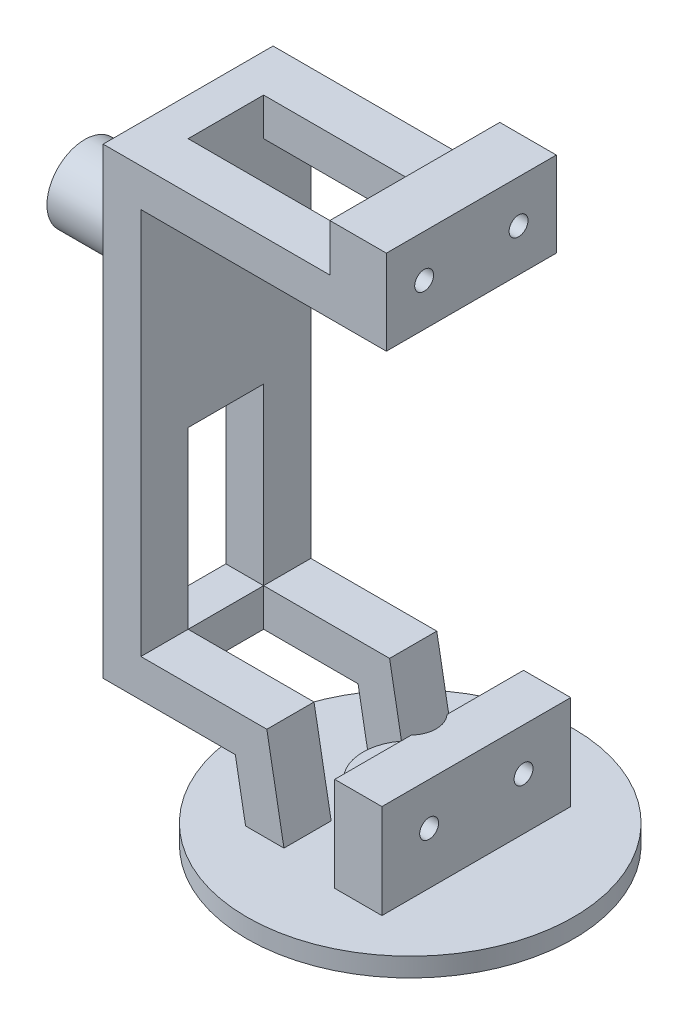
SolidWorks part; units mm, degrees
ref_plane "Front Plane" through (0, 0, 0) normal (0, 0, 1) x (1, 0, 0)
ref_plane "Top Plane" through (0, 0, 0) normal (0, 1, 0) x (1, 0, 0)
ref_plane "Right Plane" through (0, 0, 0) normal (1, 0, 0) x (0, 0, -1)
sketch "Sketch1" plane through (0, 0, 0) normal (0, 1, 0) x (1, 0, 0)
  line L0 (-20, 0) -> (20, 0) construction
  line L1 (-20, -12.5) -> (20, -12.5)
  line L2 (-20, -12.5) -> (-20, 12.5)
  line L3 (-20, 12.5) -> (20, 12.5)
  line L4 (20, -12.5) -> (20, 12.5)
  line L5 (-20, -12.5) -> (20, 12.5) construction
  line L6 (-20, 12.5) -> (20, -12.5) construction
  line L7 (0, 12.5) -> (0, -12.5) construction
  line L8 (-7.9106, 3.9553) -> (7.0894, 3.9553)
  line L9 (-7.9106, 3.9553) -> (-7.9106, -3.5447)
  line L10 (-7.9106, -3.5447) -> (7.0894, -3.5447)
  line L11 (7.0894, 3.9553) -> (7.0894, -3.5447)
  line L12 (-7.9106, 3.9553) -> (7.0894, -3.5447) construction
  line L13 (-7.9106, -3.5447) -> (7.0894, 3.9553) construction
  circle A0 centre (0, 7.9553) radius 1
  circle A1 centre (0, -7.5447) radius 1
  circle A2 centre (16, 0) radius 1
  circle A3 centre (-16, 0) radius 1
  point P0 (0, 0)
  point P8 (0, 0)
  dimension "D5" = 2
  dimension "D7" = 2
  dimension "D9" = 2
  dimension "D1" = 40
  dimension "D2" = 25
  dimension "D3" = 15
  dimension "D4" = 7.5
  dimension "D6" = 4
  dimension "D8" = 4
  dimension "D10" = 16
extrude "Boss-Extrude1" add sketch "Sketch1" along normal blind 2 contours L2 L1 L4 L3
sketch "Sketch2" plane through (0, 2, 0) normal (0, 1, 0) x (1, 0, 0)
  line L1 (2, 10) -> (7, 10)
  line L2 (2, 10) -> (2, -10)
  line L3 (2, -10) -> (7, -10)
  line L4 (7, 10) -> (7, -10)
  line L5 (20, -12.5) -> (20, 12.5) construction
  point P6 (20, 0)
  point P7 (7, 0)
  dimension "D1" = 20
  dimension "D2" = 13
  dimension "D3" = 5
extrude "Boss-Extrude2" add sketch "Sketch2" along normal blind 10
sketch "Sketch4" plane through (7, 0, 0) normal (1, 0, 0) x (0, 0, -1)
  line L0 (-7.046, 10.16) -> (2.954, 10.16) construction
  line L3 (-10, 12) -> (9.965, 12)
  line L4 (-10, 12) -> (-10, 6)
  line L5 (-10, 6) -> (9.965, 6)
  line L6 (9.965, 12) -> (9.965, 6)
  dimension "D1" = 10
  dimension "D2" = 6
extrude "Boss-Extrude3" add sketch "Sketch4" against normal up to surface (5 mm away) up to face at (2, 7, 0)
sketch "Sketch5" plane through (7, 0, 0) normal (1, 0, 0) x (0, 0, -1)
  line L0 (-5, 7.5) -> (5, 7.5) construction
  line L1 (-10, 12) -> (10, 12) construction
  circle A0 centre (5, 7.5) radius 1
  circle A1 centre (-5, 7.5) radius 1
  point P4 (0, 12)
  point P5 (0, 7.5)
  dimension "D2" = 2
  dimension "D3" = 2
  dimension "D1" = 10
  dimension "D4" = 4.5
extrude "Cut-Extrude2" cut sketch "Sketch5" against normal up to surface (5 mm away) up to face at (2, 7, 0)
sketch "Sketch6" plane through (0, 2, 0) normal (0, 1, 0) x (1, 0, 0)
  line L0 (-20, 12.5) -> (-20, -12.5) construction
  line L1 (-13.5277, 9) -> (-9.5277, 9)
  line L2 (-13.5277, 9) -> (-13.5277, -9)
  line L3 (-13.5277, -9) -> (-9.5277, -9)
  line L4 (-9.5277, 9) -> (-9.5277, -9)
  line L10 (-13.5277, 4) -> (-9.5277, 4)
  line L11 (-13.5277, 4) -> (-13.5277, -4)
  line L12 (-13.5277, -4) -> (-9.5277, -4)
  line L13 (-9.5277, 4) -> (-9.5277, -4)
  point P6 (-20, 0)
  point P7 (-13.5277, 0)
  point P12 (-13.5277, 0)
  dimension "D1" = 4
  dimension "D2" = 18
  dimension "D3" = 4
  dimension "D4" = 8
extrude "Boss-Extrude4" add sketch "Sketch6" along normal blind 10 contours L12 L2 L3 L4 | L2 L10 L4 L1 region at (-11.5277, 2, -6.5) region at (-11.5277, 2, 6.5)
sketch "Sketch8" plane through (-13.5277, 0, 0) normal (-1, 0, 0) x (0, 0, 1)
  line L1 (-9, 12) -> (-4, 12)
  line L2 (-9, 12) -> (-9, 8)
  line L3 (-9, 8) -> (-4, 8)
  line L4 (-4, 12) -> (-4, 8)
  dimension "D1" = 5
  dimension "D2" = 4
ref_plane "Plane1" through (0, 0, 0) normal (0, 0, -1) x (-1, 0, 0)
extrude "Boss-Extrude5" add sketch "Sketch8" along normal blind 10
mirror "Mirror1" about plane through (0, 0, 0) normal (0, 0, -1) of "Boss-Extrude5"
sketch "Sketch9" plane through (0, 12, 0) normal (0, 1, 0) x (1, 0, 0)
  line L0 (-23.5277, 4) -> (-9.5277, 4) construction
  line L1 (-23.5277, 9) -> (-19.5277, 9)
  line L2 (-23.5277, 9) -> (-23.5277, 4)
  line L3 (-23.5277, 4) -> (-19.5277, 4)
  line L4 (-19.5277, 9) -> (-19.5277, 4)
  dimension "D1" = 4
  dimension "D2" = 0
extrude "Boss-Extrude6" add sketch "Sketch9" along normal blind 45
mirror "Mirror2" about plane through (0, 0, 0) normal (0, 0, -1) of "Boss-Extrude5"
mirror "Mirror3" about plane through (0, 0, 0) normal (0, 0, -1) of "Boss-Extrude6"
sketch "Sketch12" plane through (-23.5277, 0, 0) normal (-1, 0, 0) x (0, 0, 1)
  line L0 (9, 57) -> (9, 8) construction
  line L1 (-9, 57) -> (9, 57)
  line L2 (-9, 57) -> (-9, 53)
  line L3 (-9, 53) -> (9, 53)
  line L4 (9, 57) -> (9, 53)
  line L5 (-10, 12) -> (10, 12) construction
  line L6 (-9, 8) -> (9, 8)
  line L7 (-9, 8) -> (-9, 12)
  line L8 (-9, 12) -> (9, 12)
  line L9 (9, 8) -> (9, 12)
  line L10 (-9, 32.5) -> (9, 32.5) construction
  line L11 (-9, 57) -> (-9, 8) construction
  line L13 (-9, 30.5) -> (9, 30.5)
  line L14 (-9, 30.5) -> (-9, 34.5)
  line L15 (-9, 34.5) -> (9, 34.5)
  line L16 (9, 30.5) -> (9, 34.5)
  line L17 (-9, 30.5) -> (9, 34.5) construction
  line L18 (-9, 34.5) -> (9, 30.5) construction
  point P18 (0, 32.5)
  dimension "D1" = 4
  dimension "D2" = 4
  dimension "D3" = 4
extrude "Boss-Extrude8" add sketch "Sketch12" against normal up to surface (4 mm away) up to face at (-19.5277, 34.5, 6.5)
sketch "Sketch13" plane through (-19.5277, 0, 0) normal (1, 0, 0) x (0, 0, -1)
  line L1 (-9, 57) -> (-4, 57)
  line L2 (-9, 57) -> (-9, 53)
  line L3 (-9, 53) -> (-4, 53)
  line L4 (-4, 57) -> (-4, 53)
  line L5 (9, 57) -> (4, 57)
  line L6 (9, 57) -> (9, 53)
  line L7 (9, 53) -> (4, 53)
  line L8 (4, 57) -> (4, 53)
extrude "Boss-Extrude9" add sketch "Sketch13" along normal blind 26
sketch "Sketch14" plane through (6.4723, 0, 0) normal (1, 0, 0) x (0, 0, -1)
  line L0 (-9, 57) -> (9, 57)
  line L1 (-9, 57) -> (-9, 53)
  line L2 (9, 57) -> (9, 53)
  line L3 (-9, 53) -> (9, 53)
  line L4 (-9, 53) -> (-4, 53) construction
extrude "Boss-Extrude10" add sketch "Sketch14" against normal blind 6
sketch "Sketch15" plane through (6.4723, 0, 0) normal (1, 0, 0) x (0, 0, -1)
  line L0 (-5, 57.5) -> (5, 57.5) construction
  line L1 (-9, 53) -> (9, 53) construction
  line L2 (-5, 7.5) -> (-5, 57.5) construction
  circle A0 centre (-5, 57.5) radius 1
  circle A1 centre (5, 57.5) radius 1
  dimension "D3" = 2
  dimension "D4" = 2
  dimension "D1" = 10
  dimension "D2" = 4.5
sketch "Sketch16" plane through (0, 57, 0) normal (0, 1, 0) x (1, 0, 0)
  line L0 (6.4723, 9) -> (6.4723, -9)
  line L1 (6.4723, 9) -> (0.4841, 9)
  line L2 (6.4723, -9) -> (0.4841, -9)
  line L3 (0.4841, 9) -> (0.4841, -9)
extrude "Boss-Extrude11" add sketch "Sketch16" along normal blind 5
extrude "Cut-Extrude3" cut sketch "Sketch15" against normal blind 6
sketch "Sketch17" plane through (0, 0, 0) normal (0, -1, 0) x (1, 0, 0)
  circle A0 centre (0, 0) radius 3
  circle A1 centre (0, 0) radius 5
  dimension "D1" = 6
  dimension "D2" = 2
sketch "Sketch18" plane through (-23.5277, 0, 0) normal (-1, 0, 0) x (0, 0, 1)
  line L0 (0, 0) -> (0, 62) construction
  line L1 (-9, 62) -> (9, 62) construction
  line L2 (-17.0412, 42) -> (24.329, 42) construction
  line L3 (12.5, 0) -> (-12.5, 0) construction
  dimension "42" = 42
extrude "Cut-Extrude5" cut sketch "Sketch17" against normal blind 6 contours A0
ref_plane "Plane2" through (0, 1, 0) normal (0, -1, 0) x (-1, 0, 0)
ref_plane "Plane3" through (0, 3, 0) normal (0, 1, 0) x (1, 0, 0)
sketch "Sketch20" plane through (0, 3, 0) normal (0, 1, 0) x (1, 0, 0)
  circle A0 centre (0, 0) radius 3
  circle A1 centre (0, 0) radius 5
  dimension "D1" = 6
  dimension "D2" = 2
sketch "Sketch23" plane through (20, 0, 0) normal (1, 0, 0) x (0, 0, -1)
  line L0 (-12.5, 2) -> (-10.5, 2)
  line L1 (-12.5, 2) -> (-12.5, 59.5)
  line L2 (12.5, 2) -> (12.5, 59.5)
  line L3 (-10.5, 2) -> (-10.5, 59.5)
  line L4 (-12.5, 2) -> (12.5, 2) construction
  line L5 (10.5, 2) -> (10.5, 59.5)
  line L6 (10.5, 2) -> (12.5, 2)
  arc A0 (12.5, 59.5) -> (-12.5, 59.5) centre (0, 59.5) ccw
  arc A1 (10.5, 59.5) -> (-10.5, 59.5) centre (0, 59.5) ccw
  dimension "D2" = 2
sketch "Sketch24" plane through (-23.5277, 0, 0) normal (-1, 0, 0) x (0, 0, 1)
  line L2 (4, 34.5) -> (4, 53) construction
  line L3 (-4, 34.5) -> (4, 34.5)
  line L4 (-4, 34.5) -> (-4, 53)
  line L5 (-4, 53) -> (4, 53)
  line L6 (4, 34.5) -> (4, 53)
  line L7 (-4, 34.5) -> (4, 53) construction
  line L8 (-4, 53) -> (4, 34.5) construction
  line L9 (4, 34.5) -> (-4, 34.5) construction
  line M1 (4, 53) -> (4, 34.5)
  line M3 (-4, 34.5) -> (-4, 53)
extrude "Boss-Extrude18" add sketch "Sketch24" against normal blind 4 contours L5 L3 M3 | L3 L5 M1 region at (-23.5277, 43.75, 0)
extrude "Boss-Extrude20" add sketch "Sketch20" against normal blind 1
sketch "Sketch26" plane through (0, 3, 0) normal (0, 1, 0) x (1, 0, 0)
  circle A0 centre (0, 0) radius 2.9983
  circle A1 centre (0, 0) radius 5
  circle A2 centre (0, 0) radius 1.5
  line M1 (2, -4.5826) -> (2, -2.2361)
  arc M2 (2, -2.2361) -> (2, 2.2361) centre (0, 0) cw
  line M3 (2, 2.2361) -> (2, 4.5826)
  arc M4 (2, 4.5826) -> (2, -4.5826) centre (0, 0) ccw
  dimension "D1" = 3
extrude "Boss-Extrude21" add sketch "Sketch26" along normal blind 1 contours A0 A2 | M4 M1 M2 M3 region at (-2.9135, 3, 0) region at (1.8779, 3, -3.4093)
sketch "Sketch27" plane through (0, 4, 0) normal (0, 1, 0) x (1, 0, 0)
  circle A0 centre (0, 0) radius 5
  circle A1 centre (0, 0) radius 2.75
  dimension "D1" = 5.5
extrude "Boss-Extrude22" add sketch "Sketch27" along normal blind 2
sketch "Sketch28" plane through (0, 6, 0) normal (0, 1, 0) x (1, 0, 0)
  circle A0 centre (0, 0) radius 2.75
extrude "Cut-Extrude10" cut sketch "Sketch28" along normal blind 10
sketch "Sketch30" plane through (-23.5277, 0, 0) normal (-1, 0, 0) x (0, 0, 1)
  line L0 (-9, 32.5) -> (9, 32.5) construction
  line L1 (-9, 57) -> (-9, 8) construction
  line L2 (9, 57) -> (9, 8) construction
  line L3 (0, 57) -> (0, 8) construction
  line L4 (-9, 57) -> (9, 57) construction
  line L5 (-9, 8) -> (9, 8) construction
sketch "Sketch31" plane through (-23.5277, 0, 0) normal (-1, 0, 0) x (0, 0, 1)
  circle A0 centre (-0.05, 43.4) radius 4
  dimension "D1" = 8
extrude "Boss-Extrude23" add sketch "Sketch31" along normal blind 11
sketch "Sketch32" plane through (0, 0, 0) normal (0, -1, 0) x (1, 0, 0)
  circle A0 centre (0, 0) radius 23.585
extrude "Boss-Extrude24" add sketch "Sketch32" against normal blind 2
sketch "Sketch33" plane through (0, 0, 0) normal (0, -1, 0) x (1, 0, 0)
  circle A0 centre (0, 0) radius 3
  dimension "D1" = 6
extrude "Cut-Extrude11" cut sketch "Sketch33" against normal blind 3
sketch "Sketch34" plane through (0, 2, 0) normal (0, 1, 0) x (1, 0, 0)
  line L2 (-10.2128, 21.7186) -> (-10.2128, 13.9525)
  line L3 (-10.2128, 13.9525) -> (10.2128, 13.9525)
  line L4 (10.2128, 21.7186) -> (10.2128, 13.9525)
  arc A0 (10.2128, 21.7186) -> (-10.2128, 21.7186) centre (0, 0) ccw
  point P7 (0, 13.9525)
  dimension "D3" = 48
extrude "Cut-Extrude12" cut sketch "Sketch34" against normal blind 10
sketch "Sketch35" plane through (0, 0, 0) normal (0, -1, 0) x (1, 0, 0)
  line L0 (-17.2908, 0) -> (-23.585, 0)
  line L1 (-10.2128, -13.9525) -> (-10.2128, -21.2591)
  arc A0 (-23.585, 0) -> (-10.2128, -21.2591) centre (0, 0) ccw
  arc A1 (-17.2908, 0) -> (-10.2128, -13.9525) centre (0, 0) ccw
extrude "Cut-Extrude13" cut sketch "Sketch35" against normal blind 4
sketch "Sketch36" plane through (0, 0, 0) normal (0, -1, 0) x (1, 0, 0)
  line L0 (-10.2128, -13.9525) -> (10.2128, -13.9525)
  arc A0 (-10.2128, -13.9525) -> (10.2128, -13.9525) centre (0, 0) ccw
extrude "Boss-Extrude25" add sketch "Sketch36" against normal blind 2
sketch "Sketch37" plane through (0, 0, 0) normal (0, -1, 0) x (1, 0, 0)
  line L3 (-23.585, 0) -> (-17.2908, 0)
  line L4 (10.2128, -21.2591) -> (10.2128, -13.9525)
  arc A6 (10.2128, -13.9525) -> (-17.2908, 0) centre (0, 0) ccw
  arc A7 (10.2128, -21.2591) -> (-23.585, 0) centre (0, 0) ccw
extrude "Cut-Extrude15" cut sketch "Sketch37" against normal up to surface (2 mm away) up to face at (-1.3725, 2, -3.2655)
sketch "Sketch38" plane through (0, 0, 9) normal (0, 0, 1) x (1, 0, 0)
  line L1 (-9.5277, 2) -> (-13.5277, 2)
  line L2 (-9.5277, 2) -> (-9.5277, 8)
  line L3 (-9.5277, 8) -> (-13.5277, 8)
  line L4 (-13.5277, 2) -> (-13.5277, 8)
extrude "Cut-Extrude16" cut sketch "Sketch38" against normal through all
sketch "Sketch39" plane through (0, 0, 9) normal (0, 0, 1) x (1, 0, 0)
  line L0 (-9.5277, 8) -> (-8.44, 2)
  line L1 (17.2908, 2) -> (-17.2908, 2) construction
  line L2 (-9.5277, 12) -> (-6.1876, 12)
  line L3 (-6.1876, 12) -> (-4.3748, 2)
  line L4 (-9.5277, 12) -> (-9.5277, 8)
  line L5 (-8.44, 2) -> (-4.3748, 2)
  dimension "D1" = 4
extrude "Boss-Extrude26" add sketch "Sketch39" against normal blind 5
mirror "Mirror4" about plane through (0, 0, 0) normal (0, 0, -1) of "Boss-Extrude26"
equation "\"inner-diameter\"= 10mm"
equation "\"outer-diameter\"= 20mm"
